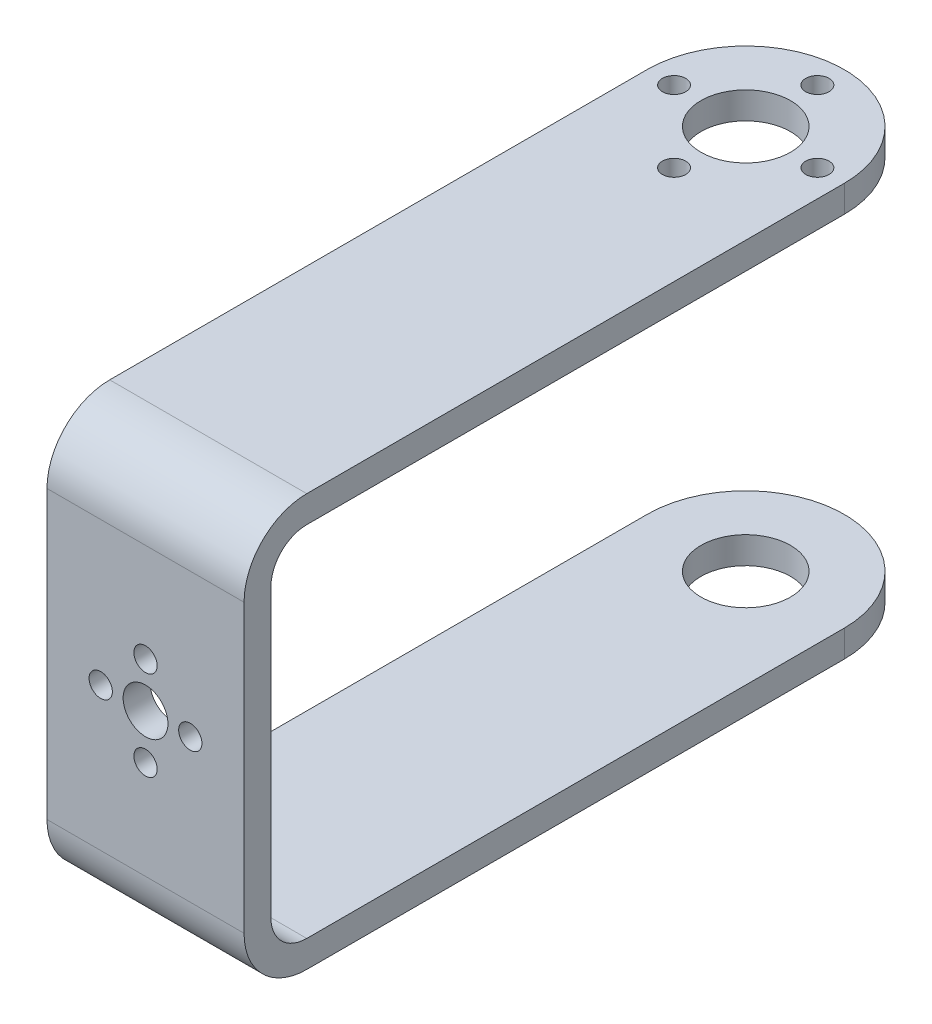
SolidWorks part; units mm, degrees
ref_plane "Front Plane" through (0, 0, 0) normal (0, 0, 1) x (1, 0, 0)
ref_plane "Top Plane" through (0, 0, 0) normal (0, 1, 0) x (1, 0, 0)
ref_plane "Right Plane" through (0, 0, 0) normal (1, 0, 0) x (0, 0, -1)
sketch "Sketch1" plane through (0, 0, 0) normal (0, 1, 0) x (1, 0, 0)
  line L5 (-11, 0) -> (11, 0)
  line L6 (-11, 0) -> (-11, -60)
  line L7 (-11, -60) -> (11, -60)
  line L8 (11, 0) -> (11, -60)
  circle A0 centre (0, 0) radius 11
  circle A1 centre (0, 0) radius 8 construction
  circle A2 centre (0, 8) radius 1.3
  circle A3 centre (8, 0) radius 1.3
  circle A4 centre (0, -8) radius 1.3
  circle A5 centre (-8, 0) radius 1.3
  circle A6 centre (0, 0) radius 5
  point P19 (0, 0)
  dimension "D1" = 16
  dimension "D3" = 2.6
  dimension "D4" = 10
  dimension "D5" = 22
  dimension "D6" = 22
  dimension "D7" = 60
  dimension "D2" = 4
extrude "Boss-Extrude1" add sketch "Sketch1" along normal blind 3 contours A0 L6 L7 L8 | A6 L5 A5 A0 A3 A4 | A6 L5 A3 A0 A5 A2 region at (0, 0, -5.4117) region at (0, 0, 5.4117) region at (0, 0, 34.261)
sketch "Sketch2" plane through (11, 0, 0) normal (1, 0, 0) x (0, 0, -1)
  line L0 (-60, 3) -> (-60, 0)
  line L1 (-67, -4) -> (-64, -4)
  line L2 (-67, -4) -> (-67, -36)
  line L3 (-67, -36) -> (-64, -36)
  line L4 (-64, -4) -> (-64, -36)
  line L5 (-60, -40) -> (-60, -43)
  arc A0 (-60, 0) -> (-64, -4) centre (-60, -4) ccw
  arc A1 (-60, 3) -> (-67, -4) centre (-60, -4) ccw
  arc A2 (-67, -36) -> (-60, -43) centre (-60, -36) ccw
  arc A3 (-64, -36) -> (-60, -40) centre (-60, -36) ccw
  line M4 (-60, 3) -> (-60, 0)
  dimension "D1" = 4
  dimension "D2" = 4
  dimension "D3" = 4
  dimension "D4" = 4
  dimension "D5" = 32
extrude "Boss-Extrude2" add sketch "Sketch2" against normal up to surface (22 mm away) contours L4 L1 L2 L3 | A1 L1 A0 M4 | A3 L3 A2 L5 region at (11, -0.4118, 63.5882) region at (11, -20, 65.5) region at (11, -39.5882, 63.5882) up to face at (-11, 1.5, 30)
ref_plane "Plane1" through (0, -40, 0) normal (0, -1, 0) x (-1, 0, 0)
sketch "Sketch6" plane through (0, -40, 0) normal (0, -1, 0) x (-1, 0, 0)
  line L1 (-11, 0) -> (11, 0)
  line L2 (-11, 0) -> (-11, -60)
  line L3 (-11, -60) -> (11, -60)
  line L4 (11, 0) -> (11, -60)
  circle A1 centre (0, 0) radius 11
  circle A2 centre (0, 0) radius 5
extrude "Boss-Extrude3" add sketch "Sketch6" along normal blind 3 contours A1 L2 L3 L4 | A2 L1 A1 | A2 L1 A1 region at (0, -40, -5.3317) region at (0, -40, 5.3317) region at (0, -40, 34.261)
sketch "Sketch7" plane through (0, 0, 67) normal (0, 0, 1) x (1, 0, 0)
  line L0 (0, -4) -> (0, -36) construction
  line L1 (-11, -4) -> (11, -4) construction
  line L2 (-11, -36) -> (11, -36) construction
  line L3 (11, -20) -> (-11, -20) construction
  line L4 (11, -4) -> (11, -36) construction
  line L5 (-11, -36) -> (-11, -4) construction
  circle A0 centre (0, -20) radius 2.5
  circle A1 centre (0, -20) radius 5
  circle A2 centre (5, -20) radius 1.3
  circle A3 centre (-5, -20) radius 1.3
  circle A4 centre (0, -25) radius 1.3
  circle A5 centre (0, -15) radius 1.3
  dimension "D1" = 2.6
  dimension "D2" = 5
  dimension "D3" = 10
extrude "Cut-Extrude1" cut sketch "Sketch7" against normal up to surface (3 mm away) contours A0 | A1 A2 | A1 A2 | A1 A4 | A1 A4 | A3 A1 | A3 A1 | A1 A5 | A1 A5 region at (0, -20, 67) region at (4.419, -20, 67) region at (5.5202, -20, 67) region at (0, -15.581, 67) region at (0, -14.4798, 67) region at (0, -25.5202, 67) region at (0, -24.419, 67) region at (-4.419, -20, 67) region at (-5.5202, -20, 67) up to face at (0, -20, 64)
equation "\"D6@Sketch1\"=\"D5@Sketch1\""
